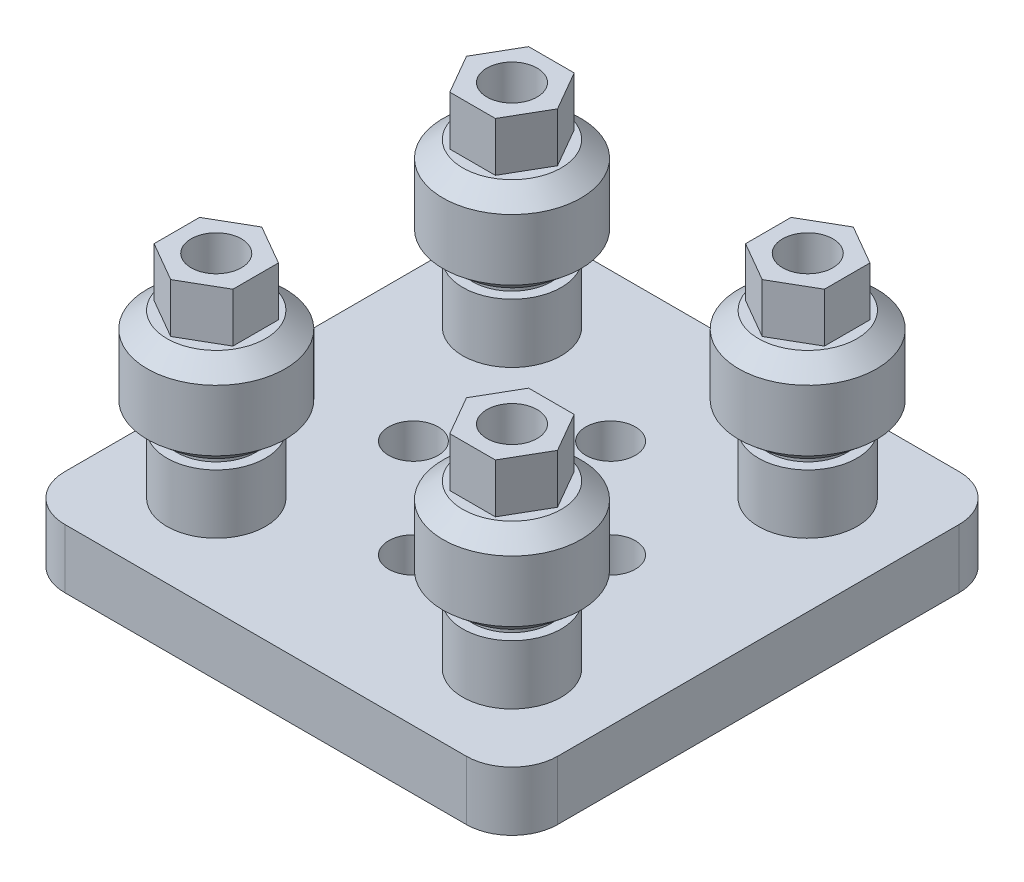
SolidWorks part; units mm, degrees
ref_plane "Спереди" through (0, 0, 0) normal (0, 0, 1) x (1, 0, 0)
ref_plane "Сверху" through (0, 0, 0) normal (0, 1, 0) x (1, 0, 0)
ref_plane "Справа" through (0, 0, 0) normal (1, 0, 0) x (0, 0, -1)
other "Configuration Table"
sketch "Эскиз1" plane through (0, 0, 0) normal (0, 1, 0) x (1, 0, 0)
  line L0 (0, 10) -> (0, 0) construction
  line L1 (-25, -25) -> (25, -25) construction
  line L2 (-25, -25) -> (-25, 20.36) construction
  line L3 (-20.36, 25) -> (25, 25) construction
  line L4 (25, -25) -> (25, 25) construction
  line L5 (-25, -25) -> (25, 25) construction
  line L6 (-25, 25) -> (25, -25) construction
  line L7 (10, 0) -> (0, 0) construction
  line L8 (0, -10) -> (0, 0) construction
  line L9 (-10, 0) -> (0, 0) construction
  line L10 (-23.641, 23.641) -> (0, 0) construction
  line L11 (25, 25) -> (-25, -25) construction
  line L12 (25, -25) -> (-25, 25) construction
  line L13 (-25, -25) -> (25, 25) construction
  line L14 (20.36, -25) -> (-20.36, -25)
  line L15 (25, -20.36) -> (25, 20.36)
  line L16 (-20.36, 25) -> (20.36, 25)
  line L17 (-25, 20.36) -> (-25, -20.36)
  circle A0 centre (-15, 15) radius 3.6
  circle A1 centre (15, 15) radius 3.6
  circle A2 centre (15, -15) radius 2.55
  circle A3 centre (-15, -15) radius 2.55
  circle A4 centre (0, 0) radius 2.51
  circle A5 centre (0, 10) radius 2.51
  circle A6 centre (10, 0) radius 2.51
  circle A7 centre (0, -10) radius 2.51
  circle A8 centre (-10, 0) radius 2.51
  arc A9 (-20.36, 25) -> (-25, 20.36) centre (-20.36, 20.36) ccw
  arc A10 (25, 20.36) -> (20.36, 25) centre (20.36, 20.36) ccw
  arc A11 (20.36, -25) -> (25, -20.36) centre (20.36, -20.36) ccw
  arc A12 (-25, -20.36) -> (-20.36, -25) centre (-20.36, -20.36) ccw
  point P0 (0, 0)
  point P19 (-23.641, 23.641)
  point P27 (0, 0)
  point P48 (0, 0)
  dimension "D4" = 7.2
  dimension "D5" = 7.2
  dimension "D6" = 5.1
  dimension "D7" = 5.1
  dimension "D8" = 5.02
  dimension "D9" = 5.02
  dimension "D12" = 9.28
  dimension "D1" = 50
  dimension "D2" = 50
  dimension "D3" = 30
  dimension "D10" = 10
  dimension "D11" = 4
  dimension "D13" = 4
extrude "Бобышка-Вытянуть1" add sketch "Эскиз1" along normal blind 6
sketch "Эскиз2" plane through (0, 0, 0) normal (0, 1, 0) x (1, 0, 0)
  circle A8 centre (-15, 15) radius 6
  circle A9 centre (-15, 15) radius 6
  circle A11 centre (15, 15) radius 6
  circle A12 centre (15, 15) radius 6
  circle A14 centre (-15, -15) radius 5.05
  circle A15 centre (-15, -15) radius 5.05
  circle A17 centre (15, -15) radius 5.05
  circle A18 centre (15, -15) radius 5.05
  dimension "D1" = 2.4
  dimension "D2" = 2.4
  dimension "D3" = 2.5
  dimension "D4" = 2.5
extrude "Вырез-Вытянуть1" cut sketch "Эскиз2" along normal blind 2
sketch "Эскиз3" plane through (0, 6, 0) normal (0, 1, 0) x (1, 0, 0)
  line L0 (-23.641, 23.641) -> (23.641, -23.641) construction
  line L1 (-15, 20) -> (-15, 10) construction
  arc A0 (-20.36, 25) -> (-25, 20.36) centre (-20.36, 20.36) ccw construction
  arc A1 (20.36, -25) -> (25, -20.36) centre (20.36, -20.36) ccw construction
  circle A4 centre (-15, 15) radius 5
  circle A5 centre (-15, 15) radius 2.55
  dimension "D1" = 10
  dimension "D2" = 5.1
extrude "втулка" add sketch "Эскиз3" along normal blind 6 separate body
sketch "Эскиз4" plane through (0, 12, 0) normal (0, 1, 0) x (1, 0, 0)
  line L0 (-15, 19) -> (-15, 11) construction
  circle A0 centre (-15, 15) radius 2.55
  circle A1 centre (-15, 15) radius 4
  dimension "D1" = 8
  dimension "D2" = 5.1
extrude "шайба" add sketch "Эскиз4" along normal blind 1
sketch3d "Трехмерный эскиз2"
  line L0 (-15, 12, -19) -> (-15, 12, -11) construction
sketch "Эскиз5" plane through (-15, 0, 0) normal (1, 0, 0) x (0, 0, -1)
  line L0 (11, 13) -> (19, 13) construction
  line L1 (19, 13) -> (11, 13) construction
  line L2 (15, 13) -> (15, 19.7752) construction
  line L3 (17.55, 13) -> (17.55, 22.5)
  line L4 (17.55, 22.5) -> (20, 22.5)
  line L5 (20, 22.5) -> (22, 20.85)
  line L6 (22, 20.85) -> (22, 14.65)
  line L7 (22, 14.65) -> (20, 13)
  line L8 (20, 13) -> (17.55, 13)
  point P8 (15, 13)
  point P11 (22, 17.75)
  point P16 (17.55, 17.75)
  point P17 (0, 0)
  point P18 (0, 0)
  point P19 (0, 0)
  point P20 (0, 0)
  dimension "D1" = 2.55
  dimension "D2" = 2
  dimension "D3" = 5
  dimension "D4" = 6.2
  dimension "D6" = 9.5
revolve "ролик" add sketch "Эскиз5" angle 360 about L2
sketch "Эскиз6" plane through (0, 22.5, 0) normal (0, 1, 0) x (1, 0, 0)
  line L0 (-17.3094, 11) -> (-19.6188, 15)
  line L1 (-19.6188, 15) -> (-17.3094, 19)
  line L2 (-17.3094, 19) -> (-12.6906, 19)
  line L3 (-12.6906, 19) -> (-10.3812, 15)
  line L4 (-10.3812, 15) -> (-12.6906, 11)
  line L5 (-12.6906, 11) -> (-17.3094, 11)
  circle A0 centre (-15, 15) radius 4 construction
  circle A2 centre (-15, 15) radius 2.55
  dimension "D1" = 8
  dimension "D2" = 5.1
extrude "гайка" add sketch "Эскиз6" along normal blind 5
pattern_circular "Круговой массив10" count 4 over 360 about axis through (0, 6, 0) along (0, -1, 0) of bodies 108
